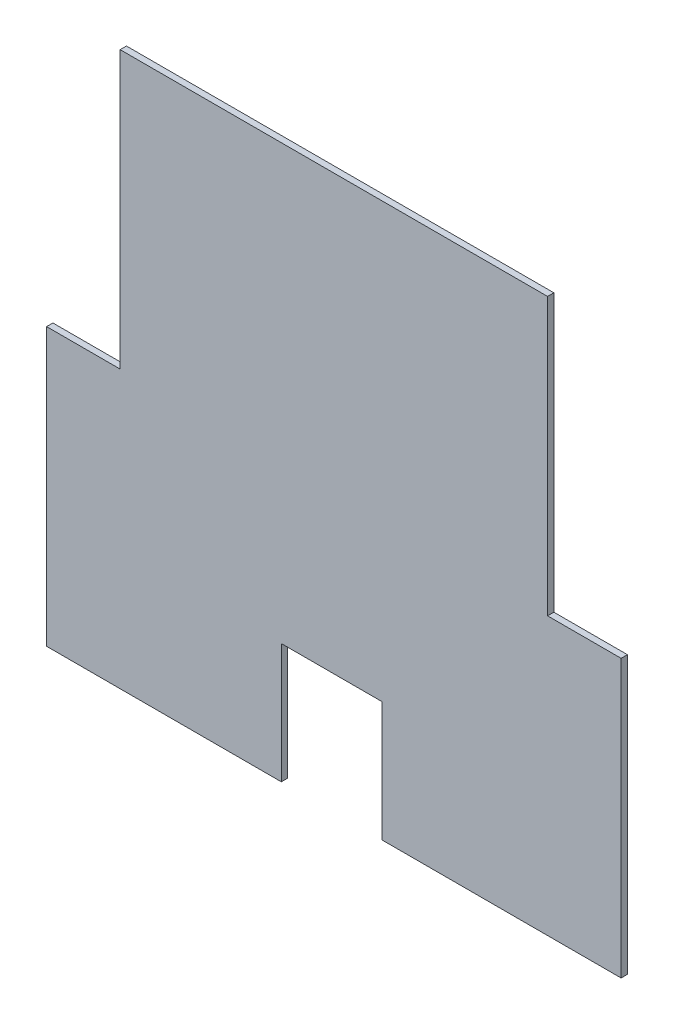
SolidWorks part; units mm, degrees
material "Oak"
ref_plane "Front Plane" through (0, 0, 0) normal (0, 0, 1) x (1, 0, 0)
ref_plane "Top Plane" through (0, 0, 0) normal (0, 1, 0) x (1, 0, 0)
ref_plane "Right Plane" through (0, 0, 0) normal (1, 0, 0) x (0, 0, -1)
sketch "Sketch1" plane through (0, 0, 0) normal (0, 0, 1) x (1, 0, 0)
  line L1 (0, 0) -> (273.4, 0)
  line L2 (0, 0) -> (0, -263.4)
  line L3 (0, -263.4) -> (273.4, -263.4)
  line L4 (273.4, 0) -> (273.4, -263.4)
  dimension "D1" = 273.4
  dimension "D2" = 263.4
extrude "Boss-Extrude1" add sketch "Sketch1" along normal blind 3
sketch "Sketch2" plane through (0, 0, 3) normal (0, 0, 1) x (1, 0, 0)
  line L1 (0, 0) -> (35, 0)
  line L2 (0, 0) -> (0, -131.64)
  line L3 (0, -131.64) -> (35, -131.64)
  line L4 (35, 0) -> (35, -131.64)
  line L9 (273.4, 0) -> (238.4, 0)
  line L10 (273.4, 0) -> (273.4, -131.64)
  line L11 (273.4, -131.64) -> (238.4, -131.64)
  line L12 (238.4, 0) -> (238.4, -131.64)
  dimension "D1" = 35
  dimension "D2" = 131.64
  dimension "D5" = 35
  dimension "D6" = 131.64
extrude "Cut-Extrude1" cut sketch "Sketch2" against normal through all
sketch "Sketch3" plane through (0, 0, 0) normal (0, 0, -1) x (-1, 0, 0)
  line L0 (0, -263.4) -> (-273.4, -263.4) construction
  line L1 (-159.7, -206.4) -> (-111.7, -206.4)
  line L2 (-159.7, -206.4) -> (-159.7, -263.4)
  line L3 (-159.7, -263.4) -> (-111.7, -263.4)
  line L4 (-111.7, -206.4) -> (-111.7, -263.4)
  line L5 (-273.4, -263.4) -> (-273.4, -131.64) construction
  dimension "D1" = 48
  dimension "D2" = 57
  dimension "D3" = 113.7
extrude "Cut-Extrude2" cut sketch "Sketch3" against normal through all
